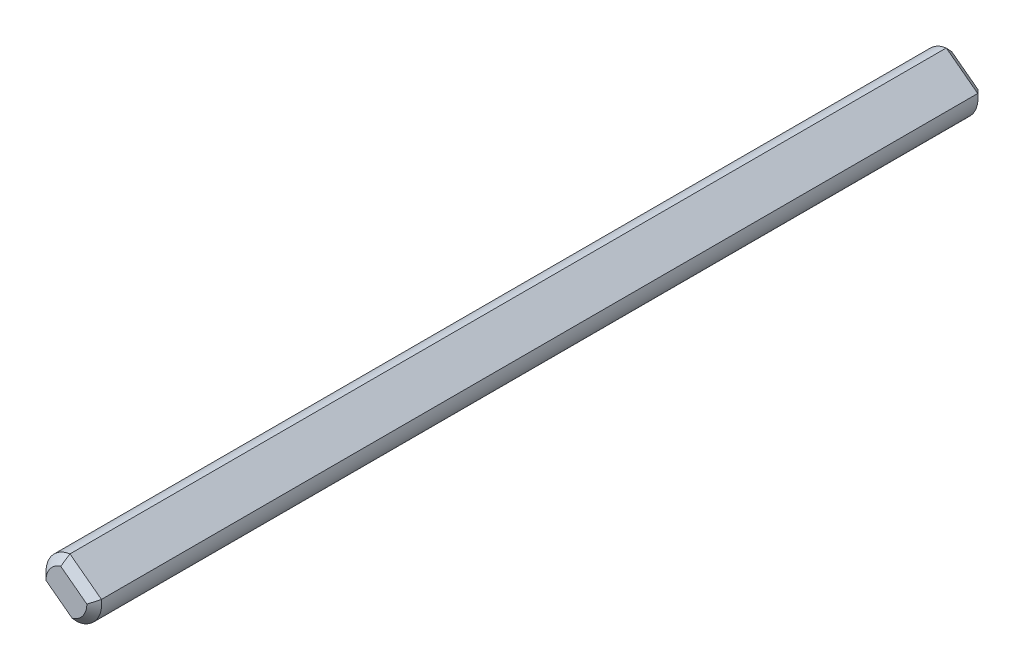
SolidWorks part; units mm, degrees
ref_plane "Front Plane" through (0, 0, 0) normal (0, 0, 1) x (1, 0, 0)
ref_plane "Top Plane" through (0, 0, 0) normal (0, 1, 0) x (1, 0, 0)
ref_plane "Right Plane" through (0, 0, 0) normal (1, 0, 0) x (0, 0, -1)
sketch "Sketch1" plane through (0, 0, 0) normal (0, 0, 1) x (1, 0, 0)
  line L0 (-20.4167, 6.7739) -> (-16.7034, 7.2967) construction
  line L7 (-16.7034, 7.2967) -> (-16.1806, 3.5833) construction
  line L8 (-20.4167, 6.7739) -> (-16.1806, 3.5833)
  line L9 (-16.7034, 7.2967) -> (-19.894, 3.0605) construction
  line L10 (-19.3712, -0.6529) -> (-23.6074, 2.5377)
  line L11 (-21.4893, 0.9424) -> (-22.1501, 0.0651) construction
  circle A1 centre (-19.894, 3.0605) radius 3.75
  dimension "D1" = 1.0983
  dimension "HexMajor" = 7.5
  dimension "OverhangAngle" = 45
extrude "Boss-Extrude1" add sketch "Sketch1" along normal blind 120 contours L8 A1 region at (-19.894, 3.0605, 0)
chamfer "End" distance 1 angle 45 8 edges at (-22.8894, 5.3166, 120) (-16.8986, 0.8044, 120) (-18.2987, 5.1786, 120) (-16.8986, 0.8044, 0) (-22.8894, 5.3166, 0) (-18.2987, 5.1786, 0) (-21.4893, 0.9424, 120) (-21.4893, 0.9424, 0)
equation "\"HexMajor\" = 7.5"
equation "\"ShaftLength\" = 120"
equation "\"OverhangAngle\"= 45"
